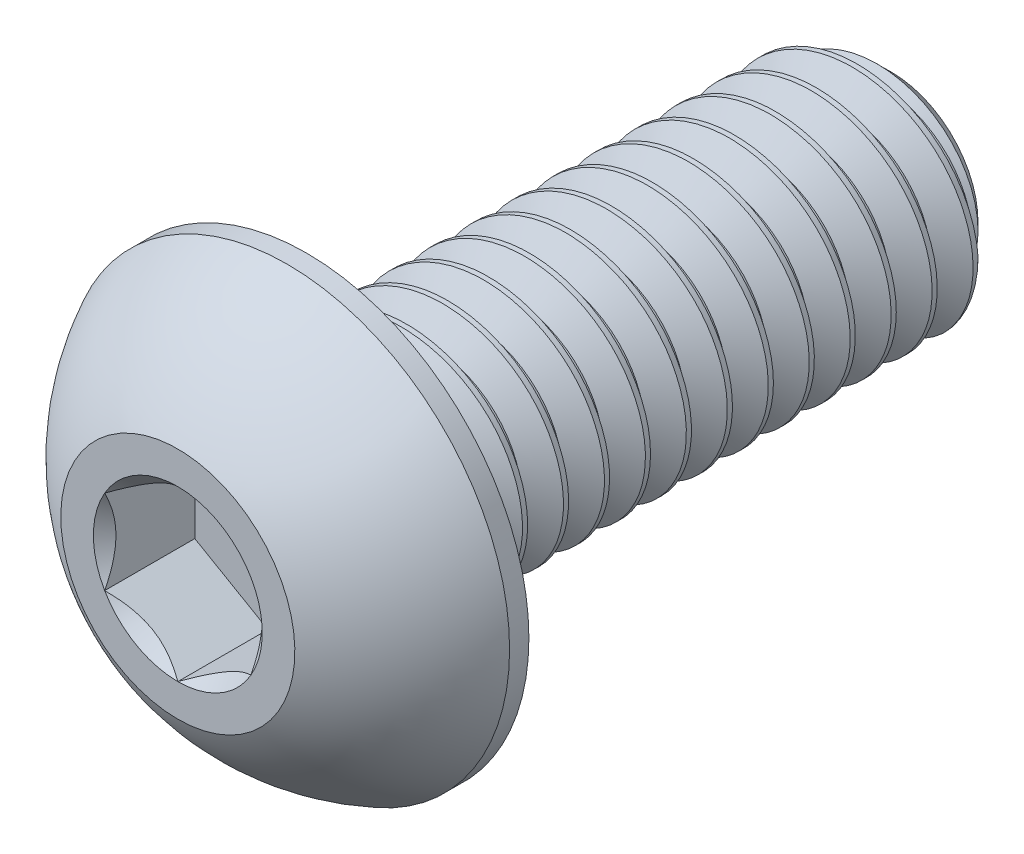
SolidWorks part; units mm, degrees
ref_plane "Front" through (0, 0, 0) normal (0, 0, 1) x (1, 0, 0)
ref_plane "Top" through (0, 0, 0) normal (0, 1, 0) x (1, 0, 0)
ref_plane "Right" through (0, 0, 0) normal (1, 0, 0) x (0, 0, -1)
sketch "Sketch1" plane through (0, 0, 0) normal (1, 0, 0) x (0, 0, -1)
  line L2 (2.2, 2) -> (12.2, 2)
  line L3 (12.2, 2) -> (12.2, 0)
  line L4 (12.2, 0) -> (2.2, 0)
  line L6 (1.87, 3.8) -> (2.2, 3.8) construction
  line L7 (12.2, 2) -> (12.2, -2) construction
  line L8 (0, 0) -> (2.2, 0) construction
  line L9 (2.2, 3.8) -> (2.2, -3.8) construction
  line L11 (2.2, 2) -> (2.2, 0)
  line L13 (0, 1.25) -> (0, -1.25) construction
  line L14 (0, 1.25) -> (0, 2) construction
  arc A3 (0, 2) -> (1.87, 3.8) centre (3.7264, 0) cw construction
  dimension "D1" = 0.33
revolve "Revolve1" add sketch "Sketch1" angle 360 mid plane about L4
sketch "Sketch3" plane through (0, 0, -12.2) normal (0, 0, -1) x (-1, 0, 0)
  circle A0 centre (0, 0) radius 2
curve "Helix/Spiral1" pitch 0.7 height 10.7 radius 2 centre (0, 0, -12.2) axis (0, 0, 1) start towards (0, 1, 0)
sketch "Sketch2" plane through (0, 0, 0) normal (1, 0, 0) x (0, 0, -1)
  line L0 (12.2, 2) -> (12.8125, 2)
  line L1 (12.8125, 2) -> (12.55, 1.5453)
  line L2 (12.55, 1.5453) -> (12.4625, 1.5453)
  line L3 (12.4625, 1.5453) -> (12.2, 2)
  line L4 (12.3312, 1.7727) -> (12.6812, 1.7727) construction
  dimension "D1" = 60
  dimension "D2" = 0.0875
  dimension "D3" = 0.35
chamfer "Chamfer1" distance 0.525 angle 45 1 edges at (0, 2, -12.2)
sweep "Cut-Sweep1" cut profiles "Sketch2" path "Helix/Spiral1" align with end faces yes
sketch "Sketch7" plane through (0, 0, 0) normal (1, 0, 0) x (0, 0, -1)
  line L6 (1.87, 3.8) -> (2.2, 3.8) construction
  line L8 (0, 0) -> (2.2, 0) construction
  line L11 (2.2, 3.8) -> (2.2, -3.8) construction
  line L12 (1.87, 3.8) -> (2.2, 3.8)
  line L13 (0, 0) -> (2.2, 0)
  line L14 (0, 1.25) -> (0, -1.25) construction
  line L15 (2.2, 3.8) -> (2.2, 0)
  line L16 (0, 2) -> (0, 0)
  arc A2 (1.87, 3.8) -> (0, 2) centre (3.7264, 0) ccw construction
  arc A3 (1.87, 3.8) -> (0, 2) centre (3.7264, 0) ccw
revolve "Revolve2" add sketch "Sketch7" angle 360 mid plane about L13
sketch "Sketch5" plane through (0, 0, 0) normal (0, 0, 1) x (1, 0, 0)
  line L1 (1.25, -0.7217) -> (1.25, 0.7217)
  line L2 (1.25, 0.7217) -> (0, 1.4434)
  line L3 (0, 1.4434) -> (-1.25, 0.7217)
  line L4 (-1.25, 0.7217) -> (-1.25, -0.7217)
  line L5 (-1.25, -0.7217) -> (0, -1.4434)
  line L6 (0, -1.4434) -> (1.25, -0.7217)
  circle A0 centre (0, 0) radius 1.25 construction
extrude "Cut-Extrude2" cut sketch "Sketch5" against normal blind 1.54
sketch "Sketch6" plane through (0, 0, 0) normal (0, 0, 1) x (1, 0, 0)
  circle A0 centre (0, 0) radius 1.4434
extrude "Cut-Extrude3" cut sketch "Sketch6" against normal blind 1.54 draft 45
sketch "Sketch9" [suppressed] plane through (0, 0, -2.2) normal (0, 0, 1) x (1, 0, 0)
  circle A2 centre (0, 0) radius 2
extrude "Boss-Extrude2" [suppressed] add sketch "Sketch9" against normal offset from surface (5 mm away) 28.575
sketch "Sketch10" plane through (0, 0, 0) normal (1, 0, 0) x (0, 0, -1)
  line L0 (12.2, 2) -> (12.2, -2) construction
  point P0 (11.15, -2)
  dimension "D1" = 1.05
equation "\"D3@Helix/Spiral1\" = \"Lg@Sketch1\" + \"D4@Helix/Spiral1\""
equation "\"D2@Sketch2\" = \"D4@Helix/Spiral1\" * .125"
equation "\"D3@Sketch2\" = \"D4@Helix/Spiral1\" * .5"
equation "\"D1@Chamfer1\" = \"D4@Helix/Spiral1\" * .75"
equation "\"D1@Cut-Extrude2\" = \"Head Ht@Sketch1\" * .7"
equation "\"D1@Sketch1\" = \"Head Ht@Sketch1\" * .15"
equation "\"D1@Sketch10\" = \"D4@Helix/Spiral1\" * 1.5"
equation "\"D1@Cut-Extrude3\" = \"D1@Cut-Extrude2\""
